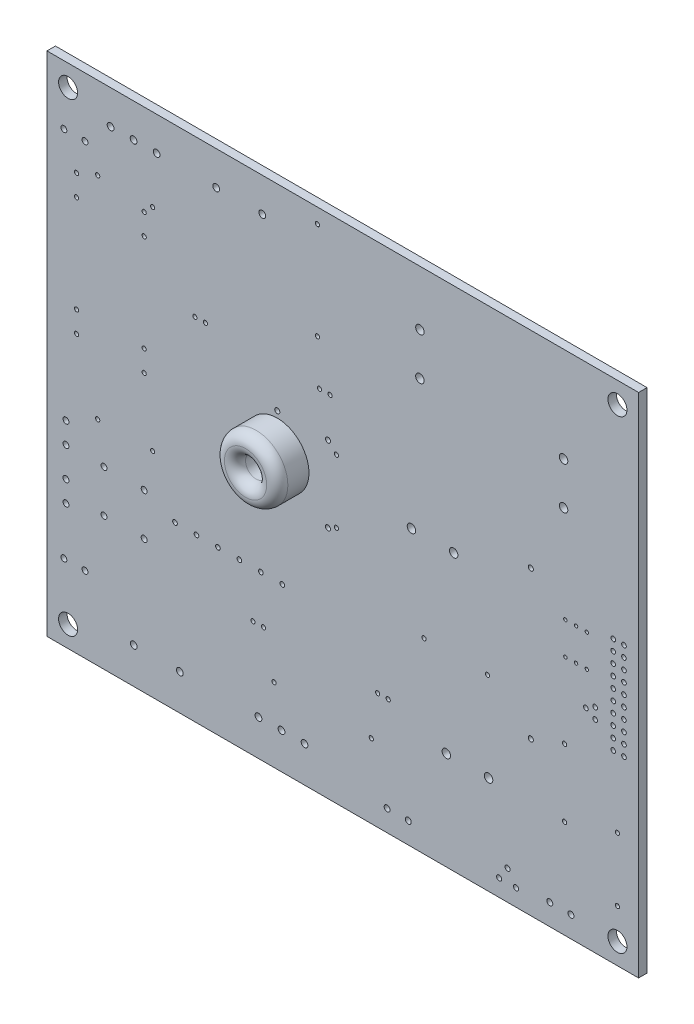
SolidWorks part; units mm, degrees
ref_plane "Спереди" through (0, 0, 0) normal (0, 0, 1) x (1, 0, 0)
ref_plane "Сверху" through (0, 0, 0) normal (0, 1, 0) x (1, 0, 0)
ref_plane "Справа" through (0, 0, 0) normal (1, 0, 0) x (0, 0, -1)
sketch "Эскиз1" plane through (0, 0, 0) normal (0, 0, 1) x (1, 0, 0)
  line L0 (-22.6071, 0) -> (23.7373, 0) construction
  line L1 (-70, -60) -> (70, -60)
  line L2 (-70, -60) -> (-70, 60)
  line L3 (-70, 60) -> (70, 60)
  line L4 (70, -60) -> (70, 60)
  line L5 (0, 0) -> (0, 31.6453) construction
  circle A0 centre (-65, -55) radius 2.25
  circle A1 centre (65, -55) radius 2.25
  circle A2 centre (65, 55) radius 2.25
  circle A3 centre (-65, 55) radius 2.25
  dimension "D3" = 4.5
  dimension "D1" = 140
  dimension "D2" = 120
  dimension "D4" = 5
  dimension "D5" = 5
extrude "Вытянуть1" add sketch "Эскиз1" along normal blind 2
sketch "Эскиз2" plane through (0, 0, 2) normal (0, 0, 1) x (1, 0, 0)
  line L0 (-70, 60) -> (-70, -60) construction
  line L1 (-70, -60) -> (70, -60) construction
  line L2 (-29.95, 52) -> (-19.05, 52) construction
  line L3 (-19.95, -51.5) -> (-9.05, -51.5) construction
  line L4 (64, 6.5) -> (66.54, 6.5) construction
  line L5 (-39.7, -21.5) -> (-11.9337, -21.5) construction
  line L14 (65, -47.75) -> (65, -32.75) construction
  line L15 (-54.95, 52) -> (-44.05, 52) construction
  line L16 (-49.45, -51.5) -> (-38.55, -51.5) construction
  line L18 (-39.7, -22.58) -> (-39.7, -21.5) construction
  line L19 (19.25, -15.75) -> (34.25, -15.75) construction
  line L20 (-1.5, -3.5) -> (-1.5, 11.5) construction
  circle A0 centre (64, 6.5) radius 0.55
  circle A1 centre (66.54, 6.5) radius 0.55
  circle A2 centre (64, 3.96) radius 0.55
  circle A3 centre (66.54, 3.96) radius 0.55
  circle A4 centre (64, 1.42) radius 0.55
  circle A5 centre (66.54, 1.42) radius 0.55
  circle A6 centre (64, -1.12) radius 0.55
  circle A7 centre (66.54, -1.12) radius 0.55
  circle A8 centre (64, -3.66) radius 0.55
  circle A9 centre (66.54, -3.66) radius 0.55
  circle A10 centre (64, -6.2) radius 0.55
  circle A11 centre (66.54, -6.2) radius 0.55
  circle A12 centre (64, -8.74) radius 0.55
  circle A13 centre (66.54, -8.74) radius 0.55
  circle A14 centre (64, -11.28) radius 0.55
  circle A15 centre (66.54, -11.28) radius 0.55
  circle A16 centre (64, -13.82) radius 0.55
  circle A17 centre (66.54, -13.82) radius 0.55
  circle A18 centre (64, -16.36) radius 0.55
  circle A19 centre (66.54, -16.36) radius 0.55
  circle A20 centre (65, -47.75) radius 0.5
  circle A21 centre (65, -32.75) radius 0.5
  circle A22 centre (-54.95, 52) radius 0.8
  circle A23 centre (-49.5, 52) radius 0.8
  circle A24 centre (-44.05, 52) radius 0.8
  circle A25 centre (-29.95, 52) radius 0.8
  circle A26 centre (-34.62, -21.5) radius 0.55
  circle A27 centre (-19.05, 52) radius 0.8
  circle A28 centre (-49.45, -51.5) radius 0.8
  circle A29 centre (-29.54, -21.5) radius 0.55
  circle A30 centre (-38.55, -51.5) radius 0.8
  circle A31 centre (-19.95, -51.5) radius 0.8
  circle A32 centre (-14.5, -51.5) radius 0.8
  circle A33 centre (-9.05, -51.5) radius 0.8
  circle A34 centre (-24.46, -21.5) radius 0.55
  circle A35 centre (-19.38, -21.5) radius 0.55
  circle A36 centre (-14.3, -21.5) radius 0.55
  circle A45 centre (-39.7, -21.5) radius 0.55
  circle A46 centre (19.25, -15.75) radius 0.5
  circle A47 centre (34.25, -15.75) radius 0.5
  circle A48 centre (-1.5, -3.5) radius 0.5
  circle A49 centre (-1.5, 11.5) radius 0.5
  dimension "D3" = 1.1
  dimension "D4" = 2.54
  dimension "D7" = 1
  dimension "D8" = 135
  dimension "D9" = 15.05
  dimension "D10" = 10.9
  dimension "D11" = 1.1
  dimension "D12" = 112
  dimension "D13" = 1.6
  dimension "D19" = 1.6
  dimension "D20" = 5.45
  dimension "D23" = 56.5
  dimension "D14" = 10.9
  dimension "D32" = 38.5
  dimension "D6" = 15
  dimension "D33" = 15
  dimension "D34" = 1
  dimension "D36" = 89.25
  dimension "D37" = 1
  dimension "D42" = 1.6
  dimension "D1" = 134
  dimension "D2" = 66.5
  dimension "D5" = 12.25
  dimension "D15" = 40.05
  dimension "D16" = 112
  dimension "D17" = 8.5
  dimension "D18" = 8.5
  dimension "D21" = 20.55
  dimension "D22" = 50.05
  dimension "D31" = 30.3
  dimension "D35" = 44.25
  dimension "D38" = 15
  dimension "D39" = 68.5
  dimension "D41" = 31.45
extrude "Вырез-Вытянуть1" cut sketch "Эскиз2" against normal blind 2
sketch "Эскиз3" plane through (0, 0, 2) normal (0, 0, 1) x (1, 0, 0)
  line L0 (-70, -60) -> (70, -60) construction
  line L1 (-70, 60) -> (-70, -60) construction
  line L2 (57.75, 4.75) -> (57.75, -2.87) construction
  line L3 (59.73, -10.875) -> (56.2465, -10.875) construction
  line L4 (59.73, -9.605) -> (59.73, -15.0734) construction
  line L5 (49, -55) -> (54, -55) construction
  line L6 (10.5, -55) -> (15.5, -55) construction
  line L7 (-65.5, -18.5) -> (-65.5, -13.5) construction
  line L8 (-65.5, -30.5) -> (-65.5, -25.5) construction
  line L9 (-70, -60) -> (70, -60) construction
  line L10 (-66, 46) -> (-61, 46) construction
  line L11 (37, -56) -> (41, -56) construction
  line L12 (52.5, -36.75) -> (52.5, -20.75) construction
  line L13 (44.5, -23.75) -> (44.5, 11.25) construction
  line L14 (52.25, 27.5) -> (52.25, 37.5) construction
  line L15 (18.25, 37) -> (18.25, 47) construction
  line L16 (16.25, 5.25) -> (26.25, 5.25) construction
  line L17 (24.5, -36.75) -> (34.5, -36.75) construction
  line L18 (-66, -42) -> (-61, -42) construction
  circle A0 centre (57.75, 4.75) radius 0.4
  circle A1 centre (57.75, -2.87) radius 0.4
  circle A2 centre (55.21, -2.87) radius 0.4
  circle A3 centre (55.21, 4.75) radius 0.4
  circle A4 centre (52.67, -2.87) radius 0.4
  circle A5 centre (52.67, 4.75) radius 0.4
  circle A6 centre (59.73, -9.605) radius 0.55
  circle A7 centre (59.73, -12.145) radius 0.55
  circle A8 centre (57.54, -10.875) radius 0.55
  circle A9 centre (49, -55) radius 0.7
  circle A10 centre (10.5, -55) radius 0.7
  circle A11 centre (54, -55) radius 0.7
  circle A12 centre (15.5, -55) radius 0.7
  circle A13 centre (-65.5, -18.5) radius 0.7
  circle A14 centre (-65.5, -13.5) radius 0.7
  circle A15 centre (-65.5, -30.5) radius 0.7
  circle A16 centre (-65.5, -25.5) radius 0.7
  circle A17 centre (37, -56) radius 0.6
  circle A18 centre (41, -56) radius 0.6
  circle A19 centre (39, -53) radius 0.6
  circle A20 centre (52.5, -36.75) radius 0.5
  circle A21 centre (52.5, -20.75) radius 0.5
  circle A22 centre (44.5, -23.75) radius 0.6
  circle A23 centre (44.5, 11.25) radius 0.6
  circle A24 centre (52.25, 27.5) radius 1
  circle A25 centre (52.25, 37.5) radius 1
  circle A26 centre (18.25, 37) radius 1
  circle A27 centre (18.25, 47) radius 1
  circle A28 centre (16.25, 5.25) radius 1
  circle A29 centre (26.25, 5.25) radius 1
  circle A30 centre (24.5, -36.75) radius 1
  circle A31 centre (34.5, -36.75) radius 1
  circle A32 centre (-66, 46) radius 0.7
  circle A33 centre (-61, 46) radius 0.7
  circle A34 centre (-66, -42) radius 0.7
  circle A35 centre (-61, -42) radius 0.7
  dimension "D1" = 0.8
  dimension "D4" = 7.62
  dimension "D5" = 1.1
  dimension "D8" = 2.54
  dimension "D9" = 127.54
  dimension "D10" = 119
  dimension "D11" = 5
  dimension "D16" = 80.5
  dimension "D17" = 5
  dimension "D18" = 41.5
  dimension "D22" = 1.2
  dimension "D23" = 4
  dimension "D24" = 2
  dimension "D25" = 3
  dimension "D28" = 1
  dimension "D32" = 1.2
  dimension "D36" = 10
  dimension "D37" = 2
  dimension "D41" = 2
  dimension "D43" = 97
  dimension "D44" = 10
  dimension "D14" = 5
  dimension "D15" = 5
  dimension "D13" = 1.4
  dimension "D30" = 16
  dimension "D35" = 35
  dimension "D20" = 1.4
  dimension "D50" = 1.4
  dimension "D53" = 5
  dimension "D54" = 4
  dimension "D56" = 5
  dimension "D58" = 18
  dimension "D2" = 64.75
  dimension "D3" = 127.75
  dimension "D6" = 50.395
  dimension "D7" = 129.73
  dimension "D12" = 5
  dimension "D19" = 4.5
  dimension "D21" = 5
  dimension "D26" = 4
  dimension "D27" = 107
  dimension "D29" = 23.25
  dimension "D31" = 122.5
  dimension "D33" = 114.5
  dimension "D34" = 36.25
  dimension "D38" = 122.25
  dimension "D39" = 87.5
  dimension "D40" = 10
  dimension "D42" = 88.25
  dimension "D45" = 65.25
  dimension "D46" = 86.25
  dimension "D47" = 10
  dimension "D48" = 23.25
  dimension "D49" = 94.5
  dimension "D51" = 4.5
  dimension "D52" = 29.5
  dimension "D55" = 106
  dimension "D57" = 4
extrude "Вырез-Вытянуть2" cut sketch "Эскиз3" against normal blind 10
sketch "Эскиз4" plane through (0, 0, 2) normal (0, 0, 1) x (1, 0, 0)
  line L0 (-15.5, -4.5) -> (-15.5, 13.5) construction
  line L1 (-70, 60) -> (-70, -60) construction
  line L2 (-70, -60) -> (70, -60) construction
  line L3 (-3.5, 13.5) -> (-3.5, -4.5) construction
  line L4 (-56.5, -28.5) -> (-47, -28.5) construction
  line L5 (-6, 33.5) -> (-6, 56.5) construction
  line L6 (-56.5, -28.5) -> (-56.5, -18.5) construction
  line L7 (-70, 60) -> (-70, -60) construction
  line L8 (-63, 5.5) -> (-63, 38.5) construction
  line L9 (-47, 5.5) -> (-47, 38.5) construction
  line L10 (-58, -9.5) -> (-45, -9.5) construction
  line L11 (-58, -9.5) -> (-58, 40.5) construction
  line L12 (-45, -9.5) -> (-45, 40.5) construction
  line L13 (-35, 23) -> (-3, 23) construction
  line L15 (-16.25, -42.5) -> (6.75, -42.5) construction
  line L16 (-21.25, -32.5) -> (10.75, -32.5) construction
  circle A0 centre (-15.5, -4.5) radius 0.6
  circle A1 centre (-15.5, 3) radius 0.6
  circle A2 centre (-15.5, 6) radius 0.6
  circle A3 centre (-15.5, 13.5) radius 0.6
  circle A4 centre (-3.5, 13.5) radius 0.6
  circle A5 centre (-3.5, -4.5) radius 0.6
  circle A6 centre (-56.5, -28.5) radius 0.7
  circle A7 centre (-56.5, -18.5) radius 0.7
  circle A8 centre (-6, 33.5) radius 0.5
  circle A9 centre (-6, 56.5) radius 0.5
  circle A10 centre (-47, -28.5) radius 0.7
  circle A11 centre (-47, -18.5) radius 0.7
  circle A12 centre (-63, 5.5) radius 0.5
  circle A13 centre (-63, 38.5) radius 0.5
  circle A14 centre (-63, 33.5) radius 0.5
  circle A15 centre (-63, 10.5) radius 0.5
  circle A16 centre (-47, 5.5) radius 0.5
  circle A17 centre (-47, 38.5) radius 0.5
  circle A18 centre (-47, 33.5) radius 0.5
  circle A19 centre (-47, 10.5) radius 0.5
  circle A20 centre (-58, -9.5) radius 0.5
  circle A21 centre (-45, -9.5) radius 0.5
  circle A22 centre (-58, 40.5) radius 0.5
  circle A23 centre (-45, 40.5) radius 0.5
  circle A34 centre (-35, 23) radius 0.5
  circle A35 centre (-3, 23) radius 0.5
  circle A36 centre (-32.5, 23) radius 0.5
  circle A37 centre (-5.5, 23) radius 0.5
  circle A40 centre (-16.25, -42.5) radius 0.5
  circle A41 centre (6.75, -42.5) radius 0.5
  circle A42 centre (-21.25, -32.5) radius 0.5
  circle A43 centre (10.75, -32.5) radius 0.5
  circle A44 centre (-18.75, -32.5) radius 0.5
  circle A45 centre (8.25, -32.5) radius 0.5
  dimension "D9" = 73.5
  dimension "D10" = 13.5
  dimension "D12" = 9.5
  dimension "D15" = 64
  dimension "D19" = 10
  dimension "D24" = 5
  dimension "D25" = 5
  dimension "D26" = 7
  dimension "D29" = 23
  dimension "D31" = 5
  dimension "D37" = 50
  dimension "D55" = 1
  dimension "D58" = 27
  dimension "D59" = 2.5
  dimension "D60" = 32
  dimension "D62" = 1
  dimension "D66" = 53.75
  dimension "D71" = 27
  dimension "D72" = 32
  dimension "D73" = 2.5
  dimension "D74" = 48.75
  dimension "D44" = 3
  dimension "D79" = 7.5
  dimension "D80" = 7.5
  dimension "D2" = 1.4
  dimension "D13" = 10
  dimension "D18" = 9.5
  dimension "D20" = 1.2
  dimension "D22" = 33
  dimension "D23" = 1
  dimension "D27" = 65.5
  dimension "D28" = 1
  dimension "D30" = 33
  dimension "D14" = 23
  dimension "D16" = 93.5
  dimension "D17" = 12
  dimension "D36" = 50
  dimension "D3" = 54.5
  dimension "D4" = 66
  dimension "D7" = 66.5
  dimension "D8" = 55.5
  dimension "D11" = 31.5
  dimension "D21" = 83
  dimension "D32" = 23
  dimension "D33" = 65.5
  dimension "D34" = 25
  dimension "D35" = 50.5
  dimension "D49" = 35
  dimension "D61" = 23
  dimension "D65" = 17.5
  dimension "D67" = 27.5
extrude "Вырез-Вытянуть3" cut sketch "Эскиз4" against normal blind 10
sketch "Эскиз5" plane through (0, 0, 2) normal (0, 0, 1) x (1, 0, 0)
  line L0 (-15.5, 3) -> (-15.5, 6) construction
  line L1 (-21.2798, 4.5) -> (-17.2511, 4.5) construction
  circle A0 centre (-15.5, 4.5) radius 2.5
  circle A1 centre (-15.5, 4.5) radius 7.5
  circle A2 centre (-15.5, 6) radius 0.6 construction
  circle A3 centre (-15.5, 3) radius 0.6 construction
  dimension "D1" = 5
  dimension "D2" = 15
extrude "Вытянуть2" add sketch "Эскиз5" along normal blind 7.5
fillet "Скругление1" radius 2.5 2 edges at (-13, 4.5, 9.5) (-8, 4.5, 9.5)
